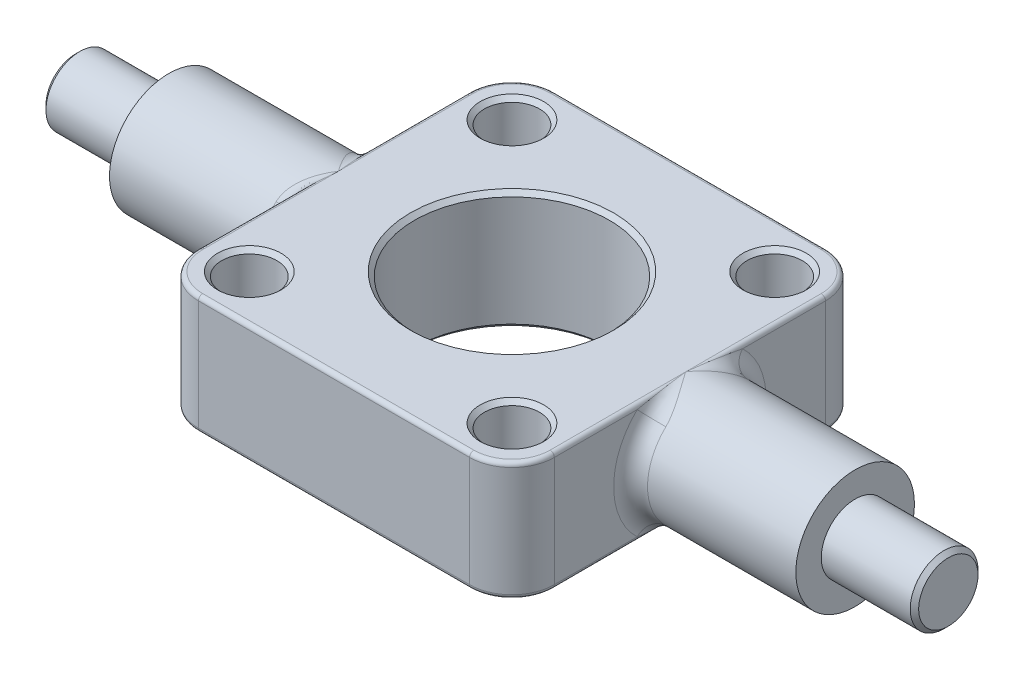
SolidWorks part; units mm, degrees
material "AlSi10Mg"
ref_plane "Front Plane" through (0, 0, 0) normal (0, 0, 1) x (1, 0, 0)
ref_plane "Top Plane" through (0, 0, 0) normal (0, 1, 0) x (1, 0, 0)
ref_plane "Right Plane" through (0, 0, 0) normal (1, 0, 0) x (0, 0, -1)
sketch "Sketch10" plane through (0, 0, 0) normal (1, 0, 0) x (0, 0, -1)
  circle A0 centre (0, 0) radius 7
  dimension "D1" = 14
extrude "Boss-Extrude2" add sketch "Sketch10" along normal mid plane 81
sketch "Sketch13" plane through (0, 0, 0) normal (1, 0, 0) x (0, 0, -1)
  circle A0 centre (0, 0) radius 4
  dimension "D1" = 8
extrude "Boss-Extrude4" add sketch "Sketch13" along normal mid plane 103
sketch "Sketch1" plane through (0, 0, 0) normal (0, 1, 0) x (1, 0, 0)
  line L0 (21, 21) -> (-21, -21) construction
  line L1 (-21, 21) -> (21, 21)
  line L2 (-21, 21) -> (-21, -21)
  line L3 (-21, -21) -> (21, -21)
  line L4 (21, 21) -> (21, -21)
  dimension "D2" = 42
extrude "Boss-Extrude1" add sketch "Sketch1" against normal mid plane 14
fillet "Fillet1" radius 5 4 edges at (-21, 0, -21) (21, 0, -21) (21, 0, 21) (-21, 0, 21)
fillet "Fillet4" radius 0.5 20 edges at (-19.5355, -7, 19.5355) (0, -7, 21) (19.5355, -7, 19.5355) (21, -7, -8) (21, -7, 8) (19.5355, -7, -19.5355) (0, -7, -21) (-19.5355, -7, -19.5355) (-21, -7, -8) (-21, -7, 8) (19.5355, 7, -19.5355) (21, 7, 8) (21, 7, -8) (19.5355, 7, 19.5355) (0, 7, 21) (-19.5355, 7, 19.5355) (-21, 7, -8) (-21, 7, 8) (-19.5355, 7, -19.5355) (0, 7, -21)
fillet "Fillet3" radius 2 12 edges at (20.8966, -6.8045, 1.6429) (21, 0, 7) (20.8966, 6.8045, 1.6429) (20.8966, 6.8045, -1.6429) (21, 0, -7) (20.8966, -6.8045, -1.6429) (-20.8966, 6.8045, -1.6429) (-20.8966, -6.8045, -1.6429) (-20.8966, -6.8045, 1.6429) (-20.8966, 6.8045, 1.6429) (-21, 0, -7) (-21, 0, 7)
sketch "Sketch3" plane through (0, -7, 0) normal (0, -1, 0) x (-1, 0, 0)
  circle A0 centre (0, 0) radius 11.5
  dimension "D1" = 23
extrude "Cut-Extrude1" cut sketch "Sketch3" against normal through all
hole_wizard "CBORE for M3 Hex Socket Head Cap Screw1" positions "Sketch4" profile "Sketch5" counterbore size "M3" standard "ISO" end condition through all
sketch "Sketch4" plane through (0, 7, 0) normal (0, -1, 0) x (-1, 0, 0)
  line L0 (-15.5, 15.5) -> (-15.5, -15.5) construction
  line L1 (-15.5, -15.5) -> (15.5, -15.5) construction
  line L2 (15.5, -15.5) -> (15.5, 15.5) construction
  line L3 (15.5, 15.5) -> (-15.5, 15.5) construction
  line L4 (-15.5, 15.5) -> (15.5, -15.5) construction
  point P0 (-15.5, 15.5)
  point P2 (15.5, 15.5)
  point P4 (15.5, -15.5)
  point P6 (-15.5, -15.5)
  dimension "D1" = 31
sketch "Sketch5" plane through (15.5, 7, -15.5) normal (1, 0, 0) x (0, 0, 1)
  line L0 (0, 0) -> (0, 14)
  line L1 (0, 14) -> (1.7, 14)
  line L3 (1.7, 14) -> (1.7, 6)
  line L4 (1.7, 6) -> (3.25, 6)
  line L5 (3.25, 6) -> (3.25, 0)
  line L7 (3.25, 0) -> (0, 0)
  line L11 (0, -6.35) -> (0, 107.95) construction
  dimension "Thru Hole Dia." = 3.4
  dimension "Thru Hole Depth" = 14
  dimension "C'Bore Dia." = 6.5
  dimension "C'Bore Depth" = 6
chamfer "Chamfer2" distance 0.5 angle 45 10 edges at (0, 7, -11.5) (0, -7, -11.5) (15.5, -7, 17.2) (-15.5, -7, 17.2) (-15.5, -7, -13.8) (15.5, -7, -13.8) (15.5, 7, -12.25) (15.5, 7, 18.75) (-15.5, 7, 18.75) (-15.5, 7, -12.25)
chamfer "Chamfer3" distance 0.5 angle 45 2 edges at (51.5, 0, -4) (-51.5, 0, -4)
